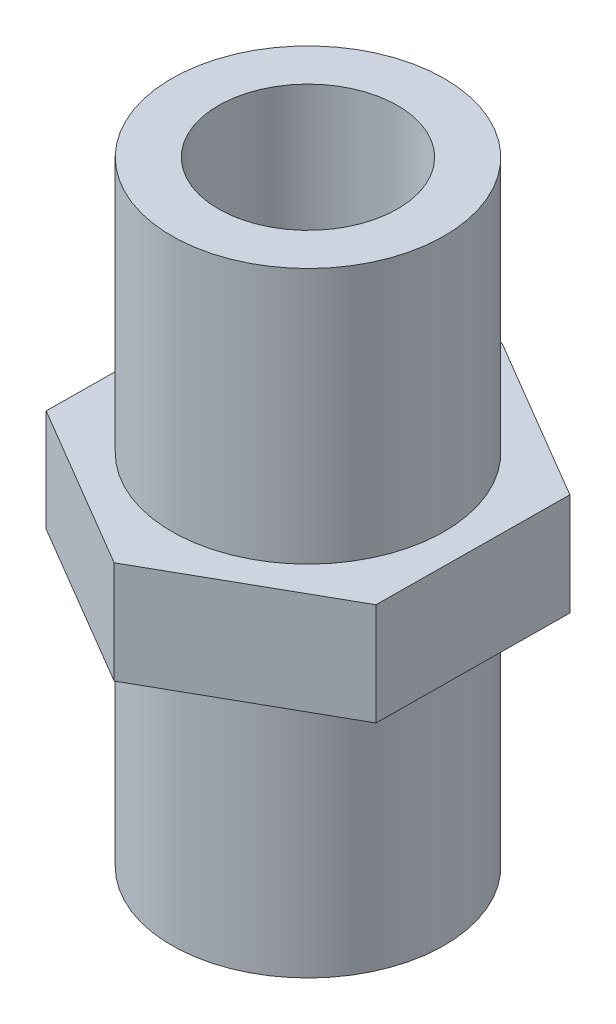
SolidWorks part; units mm, degrees
material "AISI 316  (SS)"
ref_plane "Front Plane" through (0, 0, 0) normal (0, 0, 1) x (1, 0, 0)
ref_plane "Top Plane" through (0, 0, 0) normal (0, 1, 0) x (1, 0, 0)
ref_plane "Right Plane" through (0, 0, 0) normal (1, 0, 0) x (0, 0, -1)
sketch "Sketch1" plane through (0, 0, 0) normal (0, 1, 0) x (1, 0, 0)
  circle A0 centre (0, 0) radius 10.65
  dimension "D1" = 21.3
extrude "Boss-Extrude1" add sketch "Sketch1" along normal mid plane 48
sketch "Sketch2" plane through (0, 0, 0) normal (0, 1, 0) x (1, 0, 0)
  line L1 (13.0668, 7.3887) -> (0.1346, 15.0105)
  line L2 (0.1346, 15.0105) -> (-12.9322, 7.6218)
  line L3 (-12.9322, 7.6218) -> (-13.0668, -7.3887)
  line L4 (-13.0668, -7.3887) -> (-0.1346, -15.0105)
  line L5 (-0.1346, -15.0105) -> (12.9322, -7.6218)
  line L6 (12.9322, -7.6218) -> (13.0668, 7.3887)
  circle A0 centre (0, 0) radius 13 construction
  dimension "D1" = 26
extrude "Boss-Extrude2" add sketch "Sketch2" along normal mid plane 8
sketch "Sketch3" plane through (0, 24, 0) normal (0, 1, 0) x (1, 0, 0)
  circle A0 centre (0, 0) radius 7
  dimension "D1" = 14
extrude "Cut-Extrude1" cut sketch "Sketch3" against normal through all both and the other way through all
fillet "Fillet1" radius 6 1 edges at (0, -24, 7)
